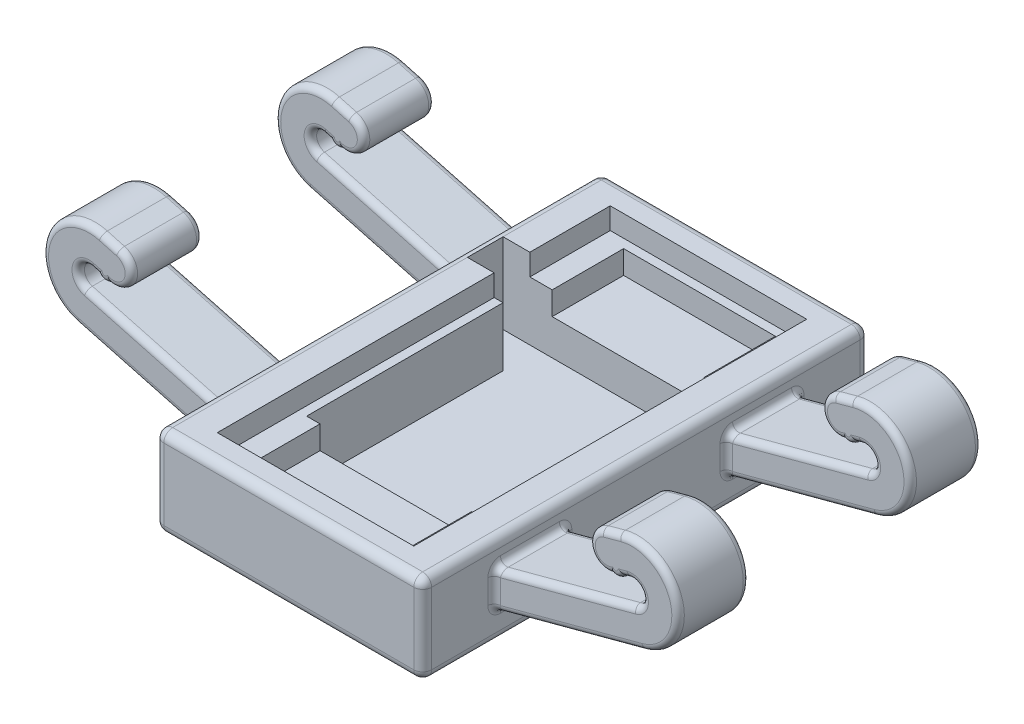
SolidWorks part; units mm, degrees
ref_plane "Front Plane" through (0, 0, 0) normal (0, 0, 1) x (1, 0, 0)
ref_plane "Top Plane" through (0, 0, 0) normal (0, 1, 0) x (1, 0, 0)
ref_plane "Right Plane" through (0, 0, 0) normal (1, 0, 0) x (0, 0, -1)
sketch "Sketch1" plane through (0, 0, 0) normal (0, 1, 0) x (1, 0, 0)
  line L1 (-19.05, -31.75) -> (19.05, -31.75)
  line L2 (-19.05, -31.75) -> (-19.05, 31.75)
  line L3 (-19.05, 31.75) -> (19.05, 31.75)
  line L4 (19.05, -31.75) -> (19.05, 31.75)
  line L5 (-19.05, -31.75) -> (19.05, 31.75) construction
  line L6 (-19.05, 31.75) -> (19.05, -31.75) construction
  point P0 (0, 0)
  dimension "D1" = 38.1
  dimension "D2" = 63.5
extrude "Boss-Extrude1" add sketch "Sketch1" against normal blind 12.7
sketch "Sketch3" plane through (0, 0, 0) normal (0, 1, 0) x (1, 0, 0)
  line L1 (-10.795, -26.67) -> (10.795, -26.67)
  line L2 (-10.795, -26.67) -> (-10.795, 26.67)
  line L3 (-10.795, 26.67) -> (10.795, 26.67)
  line L4 (10.795, -26.67) -> (10.795, 26.67)
  line L5 (-10.795, -26.67) -> (10.795, 26.67) construction
  line L6 (-10.795, 26.67) -> (10.795, -26.67) construction
  point P0 (0, 0)
  dimension "D1" = 21.59
  dimension "D2" = 53.34
extrude "Cut-Extrude2" cut sketch "Sketch3" against normal blind 6.35
sketch "Sketch4" plane through (0, 0, 31.75) normal (0, 0, 1) x (1, 0, 0)
  line L0 (-18.5804, -8.8035) -> (-40.3117, -2.9805)
  line L1 (-36.8537, 9.7821) -> (-34.4121, 9.1132)
  line L2 (-37.3804, 4.6485) -> (-38.1867, 4.8648)
  line L3 (-38.9759, 1.9207) -> (-17.2656, -3.8965)
  line L4 (-17.2656, -3.8965) -> (-18.5804, -8.8035)
  line L5 (-19.05, -12.7) -> (-19.05, 0) construction
  arc A0 (-40.3117, -2.9805) -> (-36.8537, 9.7821) centre (-38.6006, 3.4056) cw
  arc A1 (-34.4121, 9.1132) -> (-35.7415, 4.209) centre (-35.0833, 6.6628) cw
  arc A2 (-38.1867, 4.8648) -> (-38.9759, 1.9207) centre (-38.5815, 3.3928) ccw
  arc A4 (-37.3804, 4.6485) -> (-35.7415, 4.209) centre (-36.3161, 5.3415) ccw
  point P15 (-19.05, -6.35)
  point P16 (-17.923, -6.35)
  point P19 (0, 0)
  point P20 (0, 0)
  dimension "D1" = 45.212
  dimension "D6" = 2.5406
  dimension "D7" = 1.524
  dimension "D11" = 1.27
  dimension "D12" = 5.1104
  dimension "D2" = 5.08
  dimension "D3" = 22.498
  dimension "D4" = 6.6114
  dimension "D5" = 10.668
  dimension "D8" = 5.08
  dimension "D9" = 2.5317
  dimension "D10" = 3.4056
  dimension "D13" = 1.2328
  dimension "D14" = 1.3213
extrude "Boss-Extrude2" add sketch "Sketch4" along normal blind 10.16 from offset 53.34 offset against normal yes
mirror "Mirror1" about plane through (0, 0, 0) normal (0, 0, 1) of "Boss-Extrude2"
fillet "Fillet1" radius 1.27 12 edges at (0, -12.7, -31.75) (-19.05, -12.7, 0) (0, -12.7, 31.75) (19.05, -12.7, 0) (19.05, -6.35, -31.75) (-19.05, -6.35, -31.75) (19.05, -6.35, 31.75) (-19.05, -6.35, 31.75) (19.05, 0, 0) (0, 0, -31.75) (0, 0, 31.75) (-19.05, 0, 0)
fillet "Fillet2" radius 0.889 40 edges at (-19.05, -3.4184, 16.51) (-19.05, -8.6776, 16.51) (-19.05, -8.6776, -16.51) (-19.05, -3.4184, -16.51) (-29.013, -0.7488, 11.43) (-40.0535, 3.7874, 11.43) (-37.7835, 4.7566, 11.43) (-36.6451, 4.1149, 11.43) (-32.6312, 5.9981, 11.43) (-35.6329, 9.4476, 11.43) (-44.9819, 5.1346, 11.43) (-29.6809, -5.8291, 11.43) (-19.05, -6.048, 11.43) (-40.0535, 3.7874, -21.59) (-37.7835, 4.7566, -21.59) (-36.6451, 4.1149, -21.59) (-32.6312, 5.9981, -21.59) (-35.6329, 9.4476, -21.59) (-44.9819, 5.1346, -21.59) (-29.6809, -5.8291, -21.59) (-19.05, -6.048, -21.59) (-29.013, -0.7488, -21.59) (-44.9819, 5.1346, 21.59) (-35.6329, 9.4476, 21.59) (-32.6312, 5.9981, 21.59) (-36.6451, 4.1149, 21.59) (-37.7835, 4.7566, 21.59) (-40.0535, 3.7874, 21.59) (-29.013, -0.7488, 21.59) (-19.05, -6.048, 21.59) (-29.6809, -5.8291, 21.59) (-29.6809, -5.8291, -11.43) (-44.9819, 5.1346, -11.43) (-35.6329, 9.4476, -11.43) (-32.6312, 5.9981, -11.43) (-36.6451, 4.1149, -11.43) (-37.7835, 4.7566, -11.43) (-40.0535, 3.7874, -11.43) (-29.013, -0.7488, -11.43) (-19.05, -6.048, -11.43)
mirror "Mirror2" about plane through (0, 0, 0) normal (1, 0, 0) of "Mirror1"
sketch "Sketch2" plane through (0, 0, 0) normal (0, 1, 0) x (1, 0, 0)
  line L0 (12.7, 16.51) -> (-17.78, 16.51)
  line L1 (-12.7, -16.51) -> (12.7, -16.51)
  line L2 (-12.7, -16.51) -> (-12.7, 11.43)
  line L4 (12.7, -16.51) -> (12.7, 16.51)
  line L7 (-17.78, 16.51) -> (-17.78, 11.43)
  line L8 (-17.78, 11.43) -> (-12.7, 11.43)
  point P0 (0, 0)
  point P3 (-2.54, 16.51)
  point P7 (12.7, 0)
  point P10 (0, 0)
  point P11 (0, -16.51)
  dimension "D1" = 33.02
  dimension "D2" = 25.4
  dimension "D3" = 5.08
  dimension "D4" = 5.08
extrude "Cut-Extrude1" cut sketch "Sketch2" against normal blind 11.43
fillet "Fillet3" radius 0.889 40 edges at (19.05, -3.4184, -16.51) (19.05, -8.6776, -16.51) (19.05, -8.6776, 16.51) (19.05, -3.4184, 16.51) (44.9819, 5.1346, -21.59) (35.6329, 9.4476, -21.59) (32.6312, 5.9981, -21.59) (36.6451, 4.1149, -21.59) (37.7835, 4.7566, -21.59) (40.0535, 3.7874, -21.59) (29.013, -0.7488, -21.59) (19.05, -6.048, -21.59) (29.6809, -5.8291, -21.59) (29.6809, -5.8291, 11.43) (44.9819, 5.1346, 11.43) (35.6329, 9.4476, 11.43) (32.6312, 5.9981, 11.43) (36.6451, 4.1149, 11.43) (37.7835, 4.7566, 11.43) (40.0535, 3.7874, 11.43) (29.013, -0.7488, 11.43) (19.05, -6.048, 11.43) (29.013, -0.7488, -11.43) (40.0535, 3.7874, -11.43) (37.7835, 4.7566, -11.43) (36.6451, 4.1149, -11.43) (32.6312, 5.9981, -11.43) (35.6329, 9.4476, -11.43) (44.9819, 5.1346, -11.43) (29.6809, -5.8291, -11.43) (19.05, -6.048, -11.43) (40.0535, 3.7874, 21.59) (37.7835, 4.7566, 21.59) (36.6451, 4.1149, 21.59) (32.6312, 5.9981, 21.59) (35.6329, 9.4476, 21.59) (44.9819, 5.1346, 21.59) (29.6809, -5.8291, 21.59) (19.05, -6.048, 21.59) (29.013, -0.7488, 21.59)
sketch "Sketch5" plane through (0, 0, 0) normal (0, 1, 0) x (1, 0, 0)
  line L1 (-13.97, -27.94) -> (13.97, -27.94)
  line L2 (-13.97, -27.94) -> (-13.97, 27.94)
  line L3 (-13.97, 27.94) -> (13.97, 27.94)
  line L4 (13.97, -27.94) -> (13.97, 27.94)
  line L5 (-13.97, -27.94) -> (13.97, 27.94) construction
  line L6 (-13.97, 27.94) -> (13.97, -27.94) construction
  point P0 (0, 0)
  dimension "D1" = 27.94
  dimension "D2" = 55.88
extrude "Cut-Extrude3" cut sketch "Sketch5" against normal blind 3.048
